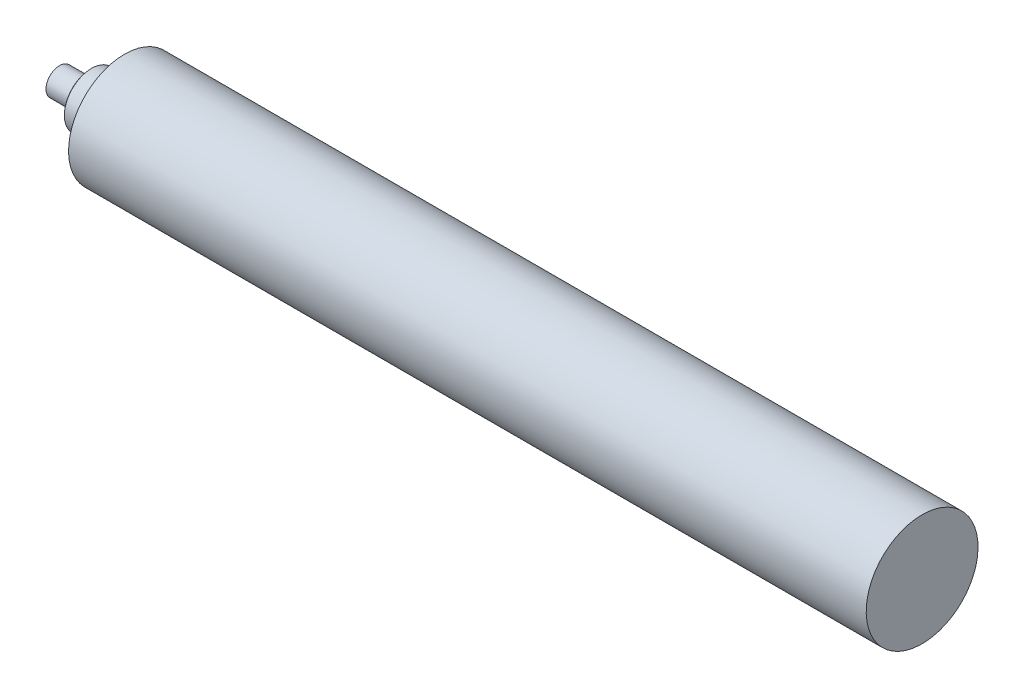
SolidWorks part; units mm, degrees
ref_plane "Front Plane" through (0, 0, 0) normal (0, 0, 1) x (1, 0, 0)
ref_plane "Top Plane" through (0, 0, 0) normal (0, 1, 0) x (1, 0, 0)
ref_plane "Right Plane" through (0, 0, 0) normal (1, 0, 0) x (0, 0, -1)
sketch "Sketch1" plane through (0, 0, 0) normal (0, 0, 1) x (1, 0, 0)
  line L0 (0, 0) -> (0, 11.938)
  line L1 (0, 11.938) -> (24.765, 11.938)
  line L2 (27.305, 14.478) -> (27.305, 22.933)
  line L3 (28.1044, 23.876) -> (57.15, 23.876)
  line L4 (57.15, 23.876) -> (57.15, 49.2125)
  line L5 (57.15, 49.2125) -> (759.206, 49.2125)
  line L6 (759.206, 49.2125) -> (759.206, 0)
  line L7 (759.206, 0) -> (0, 0)
  line L8 (27.305, 22.933) -> (28.1044, 23.876)
  arc A0 (24.765, 11.938) -> (27.305, 14.478) centre (24.765, 14.478) ccw
  point P11 (27.305, 11.938)
  dimension "D1" = 11.938
  dimension "D7" = 2.54
  dimension "D2" = 25.3365
  dimension "D3" = 49.2125
  dimension "D4" = 28.1044
  dimension "D5" = 27.305
  dimension "D6" = 702.056
  dimension "D8" = 57.15
  dimension "D9" = 22.933
revolve "Revolve1" add sketch "Sketch1" angle 360 about L7
sketch "Sketch16" plane through (0, 0, 0) normal (0, 1, 0) x (1, 0, 0)
  line L0 (0, 0) -> (0, 8.3503)
  line L1 (0, 8.3503) -> (1.905, 8.3503) construction
  line L2 (1.905, 8.3503) -> (1.905, 6.5564) construction
  line L3 (1.905, 6.5564) -> (0, 8.3503)
  line L4 (1.905, 6.5564) -> (1.905, 0)
  line L5 (-54.1337, 0) -> (54.1337, 0) construction
  line L6 (1.905, 0) -> (0, 0)
  dimension "D1" = 8.3503
  dimension "D2" = 6.5564
  dimension "D3" = 1.905
revolve "Cut-Revolve1" cut sketch "Sketch16" angle 360 about L6
sketch "Sketch19" plane through (1.905, 0, 0) normal (-1, 0, 0) x (0, 0, 1)
  circle A0 centre (0, 0) radius 6.5564
extrude "Cut-Extrude3" cut sketch "Sketch19" against normal blind 25.4
thread "Thread2" pitch 2.1167 method cut profile "Thread Profile4" start angle 0, offset 0, length 25.4, pitch 2.1167, diameter 13.1128
ref_plane "Plane4" through (1.905, 0, -6.5564) normal (0, -1, 0) x (0, 0, -1)
sketch "Thread Profile4" plane through (1.905, 0, -6.5564) normal (0, -1, 0) x (0, 0, -1)
  line L0 (0, 0) -> (0, 2.1167) construction
  line L1 (0, 0) -> (1.1457, 0.6615)
  line L2 (1.1457, 0.6615) -> (1.1457, 0.926)
  line L3 (1.1457, 0.926) -> (0, 1.5875)
  line L4 (1.1457, 0.7937) -> (0, 0.7937) construction
  line L11 (0, 0) -> (0, 1.5875)
  point P2 (0, 0)
  dimension "Pitch" = 2.1167
  dimension "Profile_Angle" = 60
  dimension "Profile_Land" = 0.2646
  dimension "Profile_Height" = 1.1457
sketch "Sketch32" plane through (0, 0, 0) normal (0, 1, 0) x (1, 0, 0)
  line L1 (-54.1337, 0) -> (54.1337, 0) construction
  line L2 (27.305, 0) -> (28.575, 0)
  line L3 (27.305, 0) -> (27.305, 6.3511)
  line L4 (27.305, 22.933) -> (27.305, -22.933) construction
  line L5 (27.305, 6.3511) -> (28.575, 0)
  dimension "D1" = 6.3511
  dimension "D2" = 1.27
  dimension "D3" = 27.305
revolve "Cut-Revolve6" cut sketch "Sketch32" angle 360 about L2
